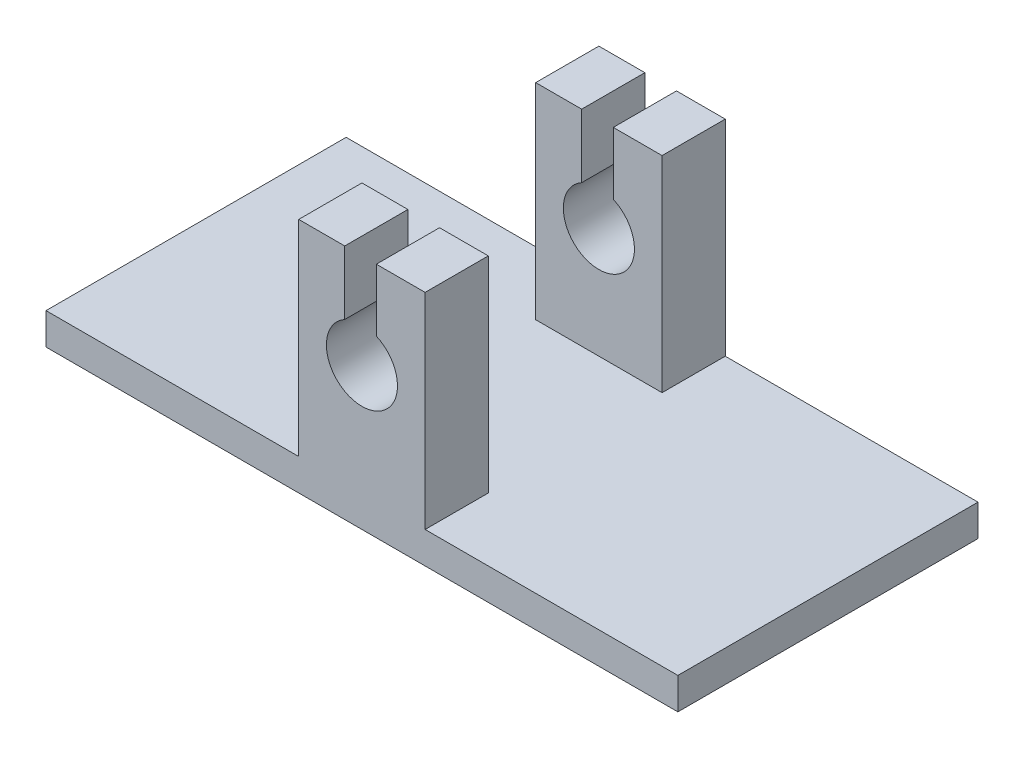
SolidWorks part; units mm, degrees
ref_plane "Front Plane" through (0, 0, 0) normal (0, 0, 1) x (1, 0, 0)
ref_plane "Top Plane" through (0, 0, 0) normal (0, 1, 0) x (1, 0, 0)
ref_plane "Right Plane" through (0, 0, 0) normal (1, 0, 0) x (0, 0, -1)
sketch "Sketch2" plane through (0, 0, 0) normal (0, 1, 0) x (1, 0, 0)
  line L1 (-127, -60.325) -> (127, -60.325)
  line L2 (-127, -60.325) -> (-127, 60.325)
  line L3 (-127, 60.325) -> (127, 60.325)
  line L4 (127, -60.325) -> (127, 60.325)
  line L5 (-127, -60.325) -> (127, 60.325) construction
  line L6 (-127, 60.325) -> (127, -60.325) construction
  point P0 (0, 0)
  dimension "D1" = 120.65
  dimension "D2" = 254
extrude "Boss-Extrude2" add sketch "Sketch2" along normal blind 12.7
sketch "Sketch4" plane through (0, 12.7, 0) normal (0, 1, 0) x (1, 0, 0)
  line L0 (-127, -60.325) -> (0, -60.325) construction
  line L1 (-127, -60.325) -> (127, -60.325) construction
  line L2 (0, -60.325) -> (0, -47.625) construction
  line L3 (0, -47.625) -> (25.4, -47.625) construction
  line L4 (25.4, -47.625) -> (25.4, -34.925) construction
  line L6 (-25.4, -60.325) -> (25.4, -60.325)
  line L7 (-25.4, -60.325) -> (-25.4, -34.925)
  line L8 (-25.4, -34.925) -> (25.4, -34.925)
  line L9 (25.4, -60.325) -> (25.4, -34.925)
  line L10 (-25.4, -60.325) -> (25.4, -34.925) construction
  line L11 (-25.4, -34.925) -> (25.4, -60.325) construction
  dimension "D1" = 12.7
  dimension "D2" = 25.4
  dimension "D3" = 12.7
extrude "Boss-Extrude3" add sketch "Sketch4" along normal blind 82.55
mirror "Mirror1" about plane through (0, 0, 0) normal (0, 0, 1) of "Boss-Extrude3"
sketch "Sketch6" plane through (0, 0, 60.325) normal (0, 0, 1) x (1, 0, 0)
  line L0 (-127, 0) -> (127, 0) construction
  line L1 (-25.4, 95.25) -> (25.4, 95.25) construction
  line L4 (-6.9118, 95.25) -> (5.7882, 95.25)
  line L5 (-6.9118, 95.25) -> (-6.9118, 69.6544)
  line L7 (5.7882, 95.25) -> (5.7882, 70.2125)
  arc A0 (-6.9118, 69.6544) -> (5.7882, 70.2125) centre (0, 57.15) ccw
  point P4 (-6.9118, 95.25)
  dimension "D1" = 28.575
  dimension "D2" = 57.15
  dimension "D3" = 12.7
extrude "Cut-Extrude1" cut sketch "Sketch6" against normal through all
